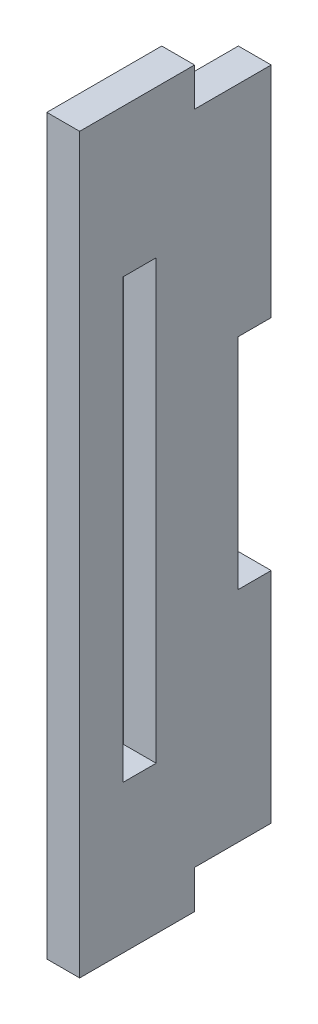
SolidWorks part; units mm, degrees
material "Balsa"
ref_plane "Alzado" through (0, 0, 0) normal (0, 0, 1) x (1, 0, 0)
ref_plane "Planta" through (0, 0, 0) normal (0, 1, 0) x (1, 0, 0)
ref_plane "Vista lateral" through (0, 0, 0) normal (1, 0, 0) x (0, 0, -1)
sketch "Croquis1" plane through (0, 0, 0) normal (1, 0, 0) x (0, 0, -1)
  line L1 (0, 0) -> (35, 0)
  line L2 (0, 0) -> (0, 120)
  line L3 (0, 120) -> (35, 120)
  line L4 (35, 0) -> (35, 120)
  dimension "D1" = 120
  dimension "D2" = 35
extrude "Saliente-Extruir1" add sketch "Croquis1" along normal blind 6
sketch "Croquis3" plane through (0, 0, 0) normal (1, 0, 0) x (0, 0, -1)
  line L0 (35, 0) -> (35, 120) construction
  line L1 (35, 39.99) -> (28.98, 39.99)
  line L2 (35, 39.99) -> (35, 80.01)
  line L3 (35, 80.01) -> (28.98, 80.01)
  line L4 (28.98, 39.99) -> (28.98, 80.01)
  line L5 (0, 120) -> (0, 0) construction
  point P6 (0, 60)
  point P9 (28.98, 60)
  dimension "D1" = 6.02
  dimension "D2" = 40.02
extrude "Cortar-Extruir1" cut sketch "Croquis3" along normal through all
sketch "Croquis4" plane through (0, 0, 0) normal (1, 0, 0) x (0, 0, -1)
  line L0 (0, 120) -> (0, 0) construction
  line L1 (7.93, 100) -> (13.98, 100)
  line L2 (7.93, 100) -> (7.93, 20)
  line L3 (7.93, 20) -> (13.98, 20)
  line L4 (13.98, 100) -> (13.98, 20)
  line L5 (28.98, 80.01) -> (28.98, 39.99) construction
  point P4 (7.93, 60)
  point P7 (0, 60)
  dimension "D1" = 80
  dimension "D2" = 15
  dimension "D3" = 6.05
extrude "Cortar-Extruir2" cut sketch "Croquis4" along normal blind 10
sketch "Croquis5" plane through (0, 0, 0) normal (1, 0, 0) x (0, 0, -1)
  line L0 (35, 0) -> (35, 39.99) construction
  line L1 (0, 120) -> (21, 120)
  line L2 (0, 120) -> (0, 127)
  line L3 (0, 127) -> (21, 127)
  line L4 (21, 120) -> (21, 127)
  line L5 (0, 0) -> (21, 0)
  line L6 (0, 0) -> (0, -7)
  line L7 (35, 80.01) -> (35, 120) construction
  line L8 (0, -7) -> (21, -7)
  line L9 (21, 0) -> (21, -7)
  dimension "D1" = 7
  dimension "D2" = 14
  dimension "D3" = 7
  dimension "D4" = 14
extrude "Saliente-Extruir2" add sketch "Croquis5" along normal blind 6
